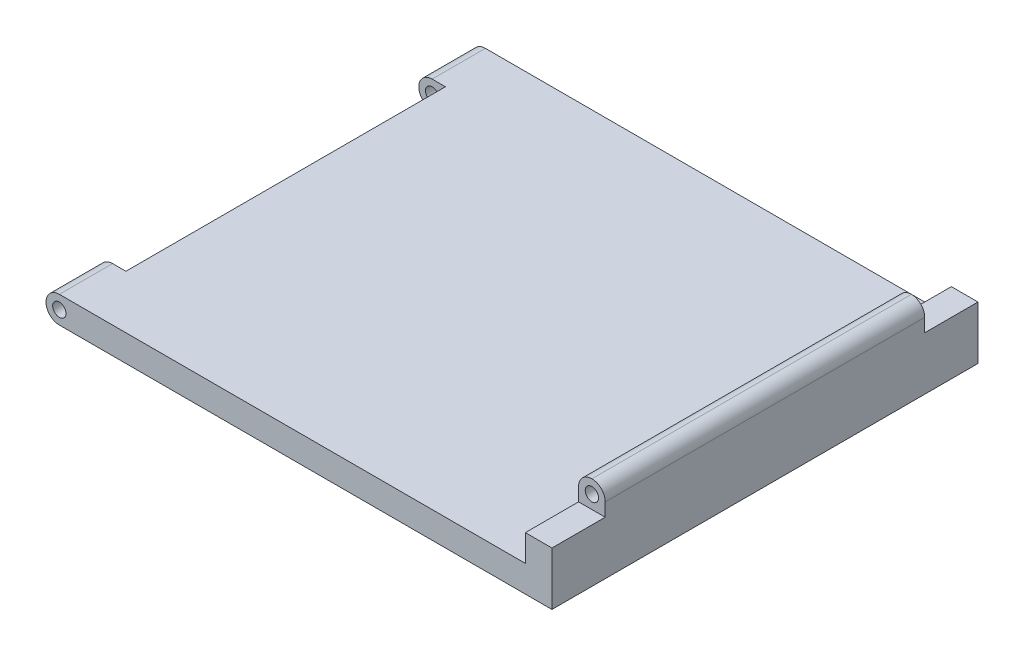
SolidWorks part; units mm, degrees
ref_plane "Front Plane" through (0, 0, 0) normal (0, 0, 1) x (1, 0, 0)
ref_plane "Top Plane" through (0, 0, 0) normal (0, 1, 0) x (1, 0, 0)
ref_plane "Right Plane" through (0, 0, 0) normal (1, 0, 0) x (0, 0, -1)
sketch "Sketch1" plane through (0, 0, 0) normal (0, 0, 1) x (1, 0, 0)
  line L0 (0, 0) -> (90, 0)
  line L1 (90, 0) -> (90, 15)
  line L2 (90, 15) -> (85, 15)
  line L3 (85, 15) -> (85, 5)
  line L4 (85, 5) -> (0, 5)
  line L5 (0, 5) -> (0, 0)
  dimension "D1" = 90
  dimension "D2" = 5
  dimension "D3" = 5
  dimension "D4" = 15
extrude "Boss-Extrude1" add sketch "Sketch1" along normal mid plane 80
sketch "Sketch2" plane through (0, 0, 0) normal (0, 0, 1) x (1, 0, 0)
  line L0 (0, 5) -> (-2.5, 5)
  line L1 (-2.5, 0) -> (0, 0)
  line L2 (0, 0) -> (0, 5)
  arc A0 (-2.5, 5) -> (-2.5, 0) centre (-2.5, 2.5) ccw
  circle A1 centre (-2.5, 2.5) radius 1.25
  dimension "D1" = 2.5
  dimension "D2" = 2.5
extrude "Boss-Extrude2" add sketch "Sketch2" along normal blind 10 from offset 30
mirror "Mirror2" about plane through (0, 0, 0) normal (0, 0, 1) of "Boss-Extrude2"
sketch "Sketch3" plane through (0, 0, 0) normal (0, 0, 1) x (1, 0, 0)
  line L0 (90, 0) -> (90, 15) construction
  line L1 (85, 15) -> (90, 15)
  line L2 (85, 15) -> (85, 10)
  line L3 (85, 10) -> (90, 10)
  line L4 (90, 15) -> (90, 10)
  dimension "D1" = 5
extrude "Cut-Extrude1" cut sketch "Sketch3" against normal blind 10 from offset 30 offset against normal yes
mirror "Mirror3" about plane through (0, 0, 0) normal (0, 0, 1) of "Cut-Extrude1"
sketch "Sketch4" plane through (0, 0, 0) normal (0, 0, 1) x (1, 0, 0)
  line L0 (90, 15) -> (85, 15) construction
  circle A0 centre (87.5, 12.5) radius 1.25
  point P5 (87.5, 15)
  dimension "D1" = 2.5
  dimension "D2" = 2.5
extrude "Cut-Extrude2" cut sketch "Sketch4" against normal through all both and the other way through all
fillet "Fillet1" radius 2.5 2 edges at (85, 15, 0) (90, 15, 0)
